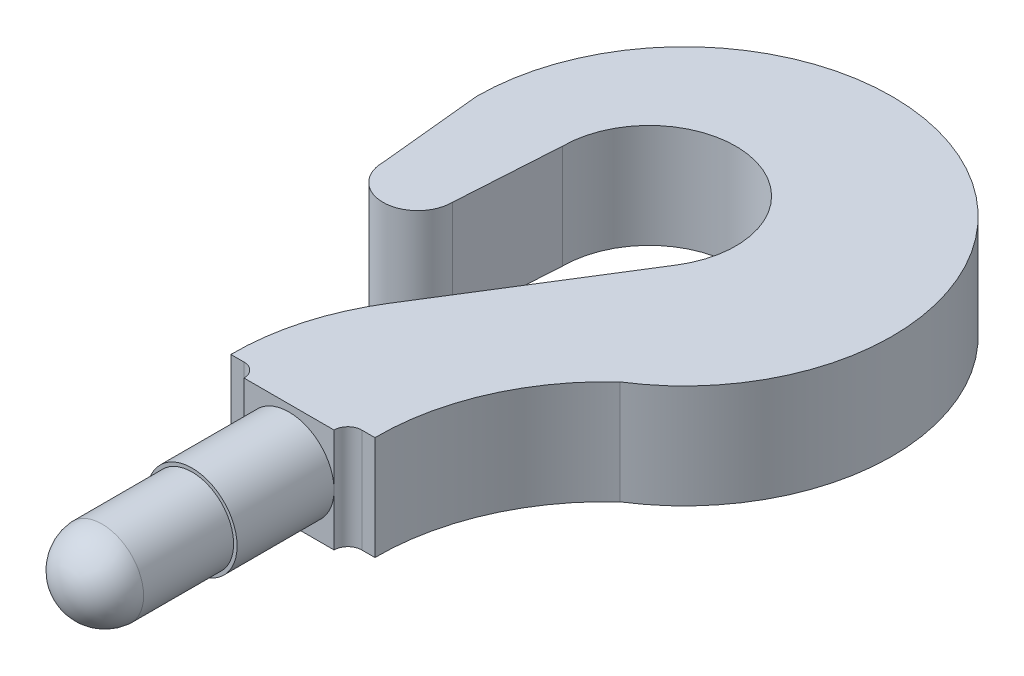
SolidWorks part; units mm, degrees
ref_plane "Piano frontale" through (0, 0, 0) normal (0, 0, 1) x (1, 0, 0)
ref_plane "Piano superiore" through (0, 0, 0) normal (0, 1, 0) x (1, 0, 0)
ref_plane "Piano destro" through (0, 0, 0) normal (1, 0, 0) x (0, 0, -1)
sketch "Schizzo1" plane through (0, 0, 0) normal (0, 0, 1) x (1, 0, 0)
  circle A0 centre (0, 0) radius 6.5
  dimension "D1" = 13
extrude "Estrusione-Estrusione1" add sketch "Schizzo1" along normal blind 14
sketch "Schizzo2" plane through (0, 0, 14) normal (0, 0, 1) x (1, 0, 0)
  circle A0 centre (0, 0) radius 6
  dimension "D1" = 12
extrude "Estrusione-Estrusione2" add sketch "Schizzo2" along normal blind 13
cosmetic thread "Filettatura cosmetica1" parameters "D2"=10.072
dome "Cupola1" faces to dome 1 distance 5.61 reverse direction no elliptical dome no face at (6, 0, 27) parameters "D1"=5.61
sketch "Schizzo3" plane through (0, 0, 0) normal (0, 1, 0) x (1, 0, 0)
  line L0 (-6.5, 0) -> (-6.5, 2)
  line L1 (-6.5, 2) -> (-10.3986, 2)
  line L2 (6.5, 0) -> (6.5, 2)
  line L3 (6.5, 2) -> (10.4014, 2)
  line L4 (0, 0) -> (0, 52) construction
  line L5 (-5.3856, 19.7928) -> (10.6006, 45.376)
  line L6 (-24.93, 52) -> (-23.43, 37)
  line L7 (-13.43, 37) -> (-12.5, 52)
  line L8 (-6.5, 0) -> (6.5, 0)
  arc A0 (21.14, 26.6671) -> (10.4014, 2) centre (43.4, 2.3054) ccw
  arc A2 (10.6006, 45.376) -> (-12.5, 52) centre (0, 52) ccw
  arc A3 (21.14, 26.6671) -> (-24.3359, 46.0594) centre (5.07, 52) ccw
  arc A4 (-5.3856, 19.7928) -> (-10.3986, 2) centre (22.6, 2.3054) ccw
  arc A5 (-23.43, 37) -> (-13.43, 37) centre (-18.43, 37) ccw
  dimension "D2" = 66
  dimension "D3" = 10
  dimension "D7" = 25
  dimension "D8" = 60
  dimension "D11" = 148
  dimension "D13" = 22.6
  dimension "D5" = 66
  dimension "D1" = 2
  dimension "D4" = 43.4
  dimension "D6" = 52
  dimension "D9" = 5.07
  dimension "D10" = 18.43
  dimension "D12" = 15
extrude "Estrusione-Estrusione3" add sketch "Schizzo3" along normal mid plane 15 contours L8 L4 L5 A4 L1 L0 | L4 L8 L2 L3 A0 A3 L6 A5 L7 A2 L5 region at (-4.1144, 0, -10.972) region at (1.0161, 0, -14.2058)
fillet "Raccordo1" radius 2 2 edges at (6.5, 0, -2) (-6.5, 0, -2)
